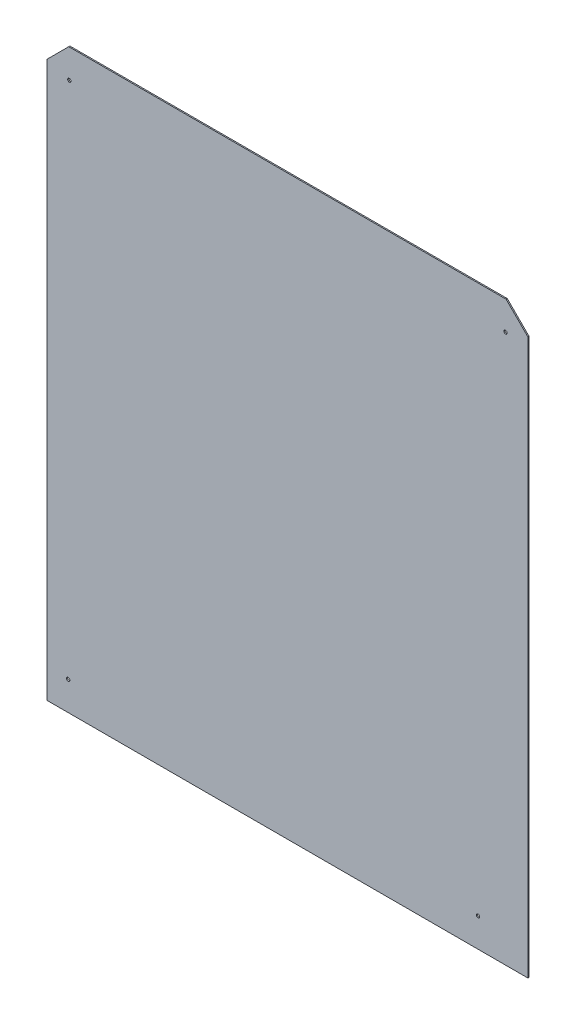
SolidWorks part; units mm, degrees
ref_plane "Front Plane" through (0, 0, 0) normal (0, 0, 1) x (1, 0, 0)
ref_plane "Top Plane" through (0, 0, 0) normal (0, 1, 0) x (1, 0, 0)
ref_plane "Right Plane" through (0, 0, 0) normal (1, 0, 0) x (0, 0, -1)
sketch "Sketch1" plane through (0, 0, 0) normal (0, 0, 1) x (1, 0, 0)
  line L0 (0, 664) -> (26, 690)
  line L1 (0, 0) -> (575, 0)
  line L2 (0, 0) -> (0, 664)
  line L3 (26, 690) -> (549, 690)
  line L4 (575, 0) -> (575, 664)
  line L5 (0, 0) -> (575, 690) construction
  line L6 (0, 690) -> (575, 0) construction
  line L7 (549, 690) -> (575, 664)
  point P4 (287.5, 345)
  dimension "D1" = 690
  dimension "D2" = 575
base flange "Base-Flange1" sketch "Sketch1" thickness 1.4 reverse thickness direction no parameters "D1"=2
sketch "Sketch6" plane through (0, 0, 0) normal (0, 0, 1) x (1, 0, 0)
  line L0 (549, 690) -> (26, 690) construction
  line L1 (575, 0) -> (575, 664) construction
  line L2 (0, 664) -> (0, 0) construction
  line L3 (0, 0) -> (575, 0) construction
  circle A0 centre (26.7, 655.5) radius 2
  circle A1 centre (548.3, 655.5) radius 2
  circle A2 centre (25.3, 34.5) radius 2
  circle A3 centre (515.5, 34.5) radius 2
  dimension "D1" = 4
  dimension "D2" = 4
  dimension "D3" = 4
  dimension "D4" = 4
  dimension "D5" = 34.5
  dimension "D6" = 34.5
  dimension "D7" = 26.7
  dimension "D8" = 26.7
  dimension "D9" = 34.5
  dimension "D10" = 34.5
  dimension "D11" = 25.3
  dimension "D12" = 59.5
extrude "Cut-Extrude1" cut sketch "Sketch6" against normal up to next normal cut yes
sketch "Bend-Lines1" [suppressed] plane through (0, 0, 0) normal (0, 1, 0) x (1, 0, 0)
sketch "Bounding-Box1" [suppressed] plane through (0, 0, 0) normal (0, 1, 0) x (1, 0, 0)
sheet metal parameters "Sheet-Metal1" thickness 1.4 parameters "D1"=2
flat pattern "Flat-Pattern1" [suppressed]
sketch "Bend-Lines2" plane through (0, 0, 0) normal (0, 1, 0) x (1, 0, 0)
sketch3d "Bounding-Box2" [suppressed]
  line L0 (-575, 690, 0) -> (-575, 0, 0) construction
  line L1 (0, 690, 0) -> (0, 0, 0) construction
  line L2 (-575, 690, 0) -> (0, 690, 0) construction
  line L3 (-575, 0, 0) -> (0, 0, 0) construction
sheet metal parameters "Sheet-Metal2" thickness 1.4 parameters "D1"=2
flat pattern "Flat-Pattern1"
sketch "Bend-Lines2" plane through (0, 0, 0) normal (0, 1, 0) x (1, 0, 0)
sketch3d "Bounding-Box2" [suppressed]
  line L0 (575, 690, 0) -> (575, 0, 0) construction
  line L1 (0, 690, 0) -> (0, 0, 0) construction
  line L2 (575, 690, 0) -> (0, 690, 0) construction
  line L3 (575, 0, 0) -> (0, 0, 0) construction
